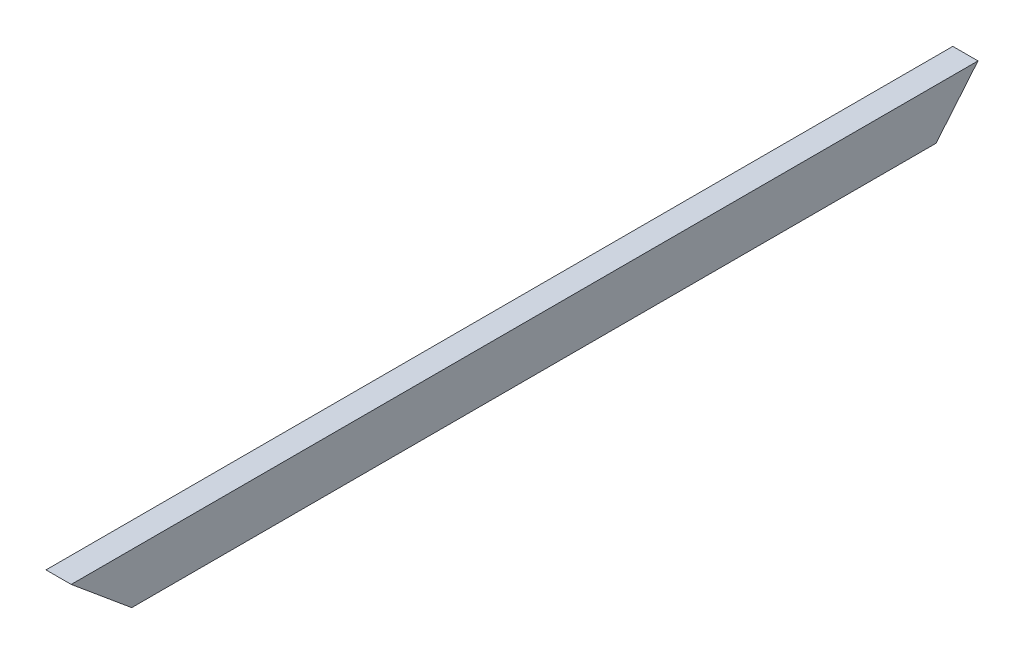
SolidWorks part; units mm, degrees
material "6063-T6"
ref_plane "Front" through (0, 0, 0) normal (0, 0, 1) x (1, 0, 0)
ref_plane "Top" through (0, 0, 0) normal (0, 1, 0) x (1, 0, 0)
ref_plane "Right" through (0, 0, 0) normal (1, 0, 0) x (0, 0, -1)
sketch "Sketch1" plane through (0, 0, 0) normal (0, 0, 1) x (1, 0, 0)
  line L0 (3.175, 3.175) -> (3.175, 22.225)
  line L1 (0, 0) -> (12.7, 0)
  line L2 (0, 0) -> (0, 25.4)
  line L3 (0, 25.4) -> (12.7, 25.4)
  line L4 (12.7, 0) -> (12.7, 25.4)
  line L5 (0, 0) -> (12.7, 25.4) construction
  line L6 (0, 25.4) -> (12.7, 0) construction
  line L7 (3.175, 22.225) -> (9.525, 22.225)
  line L8 (9.525, 3.175) -> (9.525, 22.225)
  line L9 (3.175, 3.175) -> (9.525, 3.175)
  point P4 (6.35, 12.7)
  dimension "D1" = 25.4
  dimension "D2" = 12.7
  dimension "D3" = 3.175
extrude "Boss-Extrude1" add sketch "Sketch1" along normal blind 457.2
sketch "Sketch2" plane through (12.7, 0, 0) normal (1, 0, 0) x (0, 0, -1)
  line L1 (-501.8856, 62.5833) -> (-189.4924, -197.3618) construction
  line L2 (-457.2, 25.4) -> (-426.6751, 0)
  line L3 (-457.2, 25.4) -> (-457.2, 0)
  line L4 (-457.2, 0) -> (-426.6751, 0)
  line L5 (-457.2, 0) -> (0, 0) construction
extrude "Cut-Extrude1" cut sketch "Sketch2" against normal through all
sketch "Sketch3" plane through (12.7, 0, 0) normal (1, 0, 0) x (0, 0, -1)
  line L0 (-230.9176, -252.1089) -> (29.0275, 60.2843) construction
  line L1 (-21.1356, 0) -> (0, 25.4)
  line L2 (0, 25.4) -> (0, 0)
  line L3 (0, 0) -> (-21.1356, 0)
  line L4 (-426.6751, 0) -> (0, 0) construction
extrude "Cut-Extrude2" cut sketch "Sketch3" against normal through all
